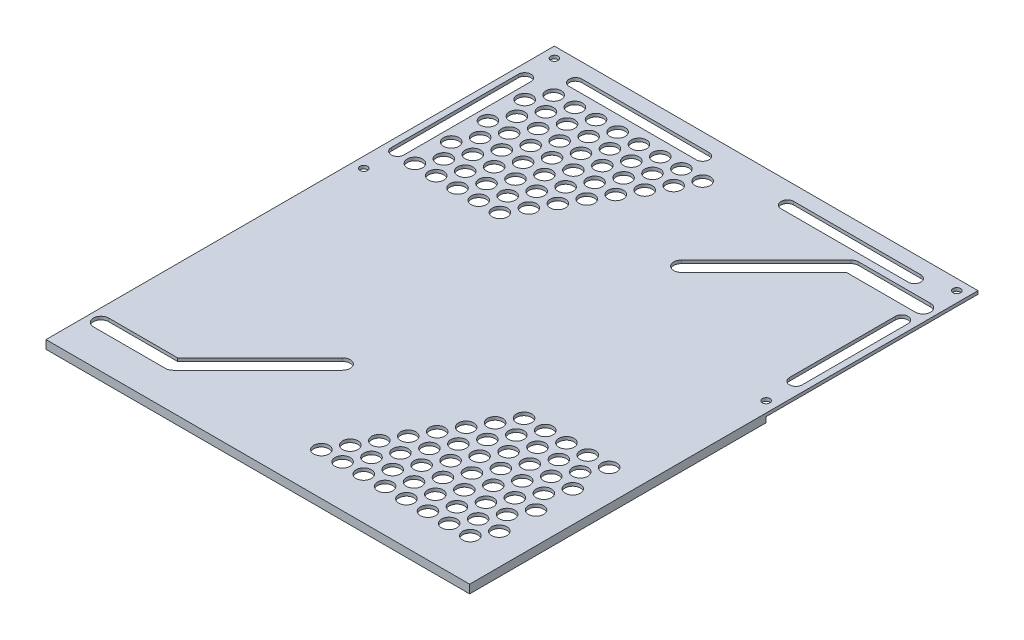
SolidWorks part; units mm, degrees
ref_plane "Front" through (0, 0, 0) normal (0, 0, 1) x (1, 0, 0)
ref_plane "Top" through (0, 0, 0) normal (0, 1, 0) x (1, 0, 0)
ref_plane "Right" through (0, 0, 0) normal (1, 0, 0) x (0, 0, -1)
sketch "Sketch1" plane through (0, 0, 0) normal (0, 1, 0) x (1, 0, 0)
  line L1 (0, 0) -> (127, 0)
  line L2 (0, 0) -> (0, 152.4)
  line L3 (0, 152.4) -> (127, 152.4)
  line L4 (127, 0) -> (127, 152.4)
  dimension "D1" = 152.4
  dimension "D2" = 127
extrude "Boss-Extrude1" add sketch "Sketch1" along normal blind 2.54
sketch "Sketch2" plane through (0, 2.54, 0) normal (0, 1, 0) x (1, 0, 0)
  line L0 (63.5, 152.4) -> (63.5, 0) construction
  line L1 (127, 152.4) -> (0, 152.4) construction
  line L2 (0, 0) -> (127, 0) construction
  line L3 (127, 76.2) -> (0, 76.2) construction
  line L4 (127, 0) -> (127, 152.4) construction
  line L5 (0, 152.4) -> (0, 0) construction
  circle A0 centre (63.5, 95.25) radius 1.016
  circle A1 centre (66.04, 95.25) radius 1.016
  circle A2 centre (68.58, 95.25) radius 1.016
  circle A3 centre (71.12, 95.25) radius 1.016
  circle A4 centre (73.66, 95.25) radius 1.016
  circle A5 centre (60.96, 95.25) radius 1.016
  circle A6 centre (58.42, 95.25) radius 1.016
  circle A7 centre (55.88, 95.25) radius 1.016
  circle A8 centre (53.34, 95.25) radius 1.016
  point P14 (63.5, 76.2)
  dimension "D1" = 2.032
  dimension "D4" = 57.15
  dimension "D2" = 5
  dimension "D3" = 5
sketch "Sketch5" plane through (0, 0, 0) normal (0, 1, 0) x (1, 0, 0)
  line L0 (63.5, 152.4) -> (63.5, 0) construction
  line L1 (0, 88.9) -> (127, 88.9)
  line L2 (0, 88.9) -> (0, 152.4)
  line L3 (0, 152.4) -> (127, 152.4)
  line L4 (127, 88.9) -> (127, 152.4)
  line L5 (0, 88.9) -> (127, 152.4) construction
  line L6 (0, 152.4) -> (127, 88.9) construction
  line L7 (127, 152.4) -> (0, 152.4) construction
  point P0 (63.5, 120.65)
  dimension "D1" = 63.5
  dimension "D2" = 127
extrude "Cut-Extrude2" cut sketch "Sketch5" along normal blind 1.5875
sketch "Sketch9" plane through (0, 2.54, 0) normal (0, 1, 0) x (1, 0, 0)
  line L0 (50.8, 38.1) -> (25.4, 12.7) construction
  line L1 (52.4164, 36.4836) -> (27.0164, 11.0836)
  line L2 (49.1836, 39.7164) -> (23.7836, 14.3164)
  line L3 (25.4, 12.7) -> (3.81, 12.7) construction
  line L4 (25.4, 10.414) -> (3.81, 10.414)
  line L5 (25.4, 14.986) -> (3.81, 14.986)
  line L6 (63.5, 152.4) -> (63.5, 0) construction
  line L7 (127, 76.2) -> (0, 76.2) construction
  line L8 (76.2, 114.3) -> (101.6, 139.7) construction
  line L9 (74.5836, 115.9164) -> (99.9836, 141.3164)
  line L10 (77.8164, 112.6836) -> (103.2164, 138.0836)
  line L11 (101.6, 139.7) -> (123.19, 139.7) construction
  line L12 (101.6, 141.986) -> (123.19, 141.986)
  line L13 (101.6, 137.414) -> (123.19, 137.414)
  arc A0 (52.4164, 36.4836) -> (49.1836, 39.7164) centre (50.8, 38.1) ccw
  arc A1 (23.7836, 14.3164) -> (27.0164, 11.0836) centre (25.4, 12.7) ccw
  arc A2 (25.4, 10.414) -> (25.4, 14.986) centre (25.4, 12.7) ccw
  arc A3 (3.81, 14.986) -> (3.81, 10.414) centre (3.81, 12.7) ccw
  arc A4 (74.5836, 115.9164) -> (77.8164, 112.6836) centre (76.2, 114.3) ccw
  arc A5 (103.2164, 138.0836) -> (99.9836, 141.3164) centre (101.6, 139.7) ccw
  arc A6 (101.6, 141.986) -> (101.6, 137.414) centre (101.6, 139.7) ccw
  arc A7 (123.19, 137.414) -> (123.19, 141.986) centre (123.19, 139.7) ccw
  point P2 (38.1, 25.4)
  point P7 (14.605, 12.7)
  point P23 (88.9, 127)
  point P28 (112.395, 139.7)
  point P35 (63.5, 76.2)
  dimension "D1" = 2.286
  dimension "D2" = 2.286
  dimension "D3" = 12.7
  dimension "D4" = 38.1
  dimension "D5" = 38.1
  dimension "D6" = 63.5
  dimension "D7" = 59.69
  dimension "D8" = 2
extrude "Cut-Extrude5" cut sketch "Sketch9" against normal through all contours A6 L9 A4 L10 L13 | A5 A6 L13 L10 | L13 A7 L12 A5 L10 | A2 L1 A0 L2 L5 | A1 A2 L5 L2 | L5 A3 L4 A1 L2 region at (39.3797, 2.54, -26.6777) region at (25.3939, 2.54, -12.7146) region at (12.7962, 2.54, -12.6976) region at (87.6203, 2.54, -125.7223) region at (101.6061, 2.54, -139.6854) region at (114.2038, 2.54, -139.7024)
sketch "Sketch10" plane through (0, 2.54, 0) normal (0, 1, 0) x (1, 0, 0)
  line L0 (127, 76.2) -> (0, 76.2) construction
  line L1 (63.5, 152.4) -> (63.5, 0) construction
  circle A1 centre (82.55, 12.7) radius 2.286
  circle A2 centre (85.7277, 18.2039) radius 2.286
  circle A3 centre (88.9053, 23.7078) radius 2.286
  circle A4 centre (92.083, 29.2117) radius 2.286
  circle A5 centre (95.2607, 34.7156) radius 2.286
  circle A6 centre (98.4384, 40.2195) radius 2.286
  circle A7 centre (101.616, 45.7234) radius 2.286
  circle A8 centre (104.7937, 51.2273) radius 2.286
  circle A9 centre (92.1245, 18.2039) radius 2.286
  circle A10 centre (95.3021, 23.7078) radius 2.286
  circle A11 centre (98.4798, 29.2117) radius 2.286
  circle A12 centre (101.6575, 34.7156) radius 2.286
  circle A13 centre (104.8352, 40.2195) radius 2.286
  circle A14 centre (108.0128, 45.7234) radius 2.286
  circle A15 centre (111.1905, 51.2273) radius 2.286
  circle A16 centre (88.9468, 12.7) radius 2.286
  circle A17 centre (98.5212, 18.2039) radius 2.286
  circle A18 centre (101.6989, 23.7078) radius 2.286
  circle A19 centre (104.8766, 29.2117) radius 2.286
  circle A20 centre (108.0543, 34.7156) radius 2.286
  circle A21 centre (111.2319, 40.2195) radius 2.286
  circle A22 centre (114.4096, 45.7234) radius 2.286
  circle A23 centre (117.5873, 51.2273) radius 2.286
  circle A24 centre (95.3436, 12.7) radius 2.286
  circle A25 centre (101.8105, 12.7) radius 2.286
  circle A26 centre (104.9882, 18.2039) radius 2.286
  circle A27 centre (108.1659, 23.7078) radius 2.286
  circle A28 centre (111.3436, 29.2117) radius 2.286
  circle A29 centre (114.5212, 34.7156) radius 2.286
  circle A30 centre (117.6989, 40.2195) radius 2.286
  circle A31 centre (108.1605, 12.7) radius 2.286
  circle A32 centre (111.3382, 18.2039) radius 2.286
  circle A33 centre (114.5159, 23.7078) radius 2.286
  circle A34 centre (117.6936, 29.2117) radius 2.286
  circle A35 centre (114.5105, 12.7) radius 2.286
  circle A36 centre (117.6882, 18.2039) radius 2.286
  circle A37 centre (44.582, 139.5661) radius 2.286
  circle A38 centre (41.4043, 134.0622) radius 2.286
  circle A39 centre (38.2266, 128.5583) radius 2.286
  circle A40 centre (35.0489, 123.0544) radius 2.286
  circle A41 centre (31.8713, 117.5505) radius 2.286
  circle A42 centre (28.6936, 112.0466) radius 2.286
  circle A43 centre (25.5159, 106.5427) radius 2.286
  circle A44 centre (22.3382, 101.0388) radius 2.286
  circle A45 centre (35.0075, 134.0622) radius 2.286
  circle A46 centre (31.8298, 128.5583) radius 2.286
  circle A47 centre (28.6522, 123.0544) radius 2.286
  circle A48 centre (25.4745, 117.5505) radius 2.286
  circle A49 centre (22.2968, 112.0466) radius 2.286
  circle A50 centre (19.1191, 106.5427) radius 2.286
  circle A51 centre (15.9415, 101.0388) radius 2.286
  circle A52 centre (38.1852, 139.5661) radius 2.286
  circle A53 centre (28.6107, 134.0622) radius 2.286
  circle A54 centre (25.433, 128.5583) radius 2.286
  circle A55 centre (22.2554, 123.0544) radius 2.286
  circle A56 centre (19.0777, 117.5505) radius 2.286
  circle A57 centre (15.9, 112.0466) radius 2.286
  circle A58 centre (12.7223, 106.5427) radius 2.286
  circle A59 centre (9.5447, 101.0388) radius 2.286
  circle A60 centre (31.7884, 139.5661) radius 2.286
  circle A61 centre (25.3214, 139.5661) radius 2.286
  circle A62 centre (22.1438, 134.0622) radius 2.286
  circle A63 centre (18.9661, 128.5583) radius 2.286
  circle A64 centre (15.7884, 123.0544) radius 2.286
  circle A65 centre (12.6107, 117.5505) radius 2.286
  circle A66 centre (9.4331, 112.0466) radius 2.286
  circle A67 centre (18.9714, 139.5661) radius 2.286
  circle A68 centre (15.7938, 134.0622) radius 2.286
  circle A69 centre (12.6161, 128.5583) radius 2.286
  circle A70 centre (9.4384, 123.0544) radius 2.286
  circle A71 centre (12.6214, 139.5661) radius 2.286
  circle A72 centre (9.4438, 134.0622) radius 2.286
  circle A73 centre (76.2, 12.7) radius 2.286
  circle A74 centre (79.3777, 18.2039) radius 2.286
  circle A75 centre (82.5553, 23.7078) radius 2.286
  circle A76 centre (85.733, 29.2117) radius 2.286
  circle A77 centre (88.9107, 34.7156) radius 2.286
  circle A78 centre (92.0884, 40.2195) radius 2.286
  circle A79 centre (95.266, 45.7234) radius 2.286
  circle A80 centre (98.4437, 51.2273) radius 2.286
  circle A81 centre (69.85, 12.7) radius 2.286
  circle A82 centre (73.0277, 18.2039) radius 2.286
  circle A83 centre (76.2053, 23.7078) radius 2.286
  circle A84 centre (79.383, 29.2117) radius 2.286
  circle A85 centre (82.5607, 34.7156) radius 2.286
  circle A86 centre (85.7384, 40.2195) radius 2.286
  circle A87 centre (88.916, 45.7234) radius 2.286
  circle A88 centre (92.0937, 51.2273) radius 2.286
  circle A89 centre (28.6882, 101.0388) radius 2.286
  circle A90 centre (31.8659, 106.5427) radius 2.286
  circle A91 centre (35.0436, 112.0466) radius 2.286
  circle A92 centre (38.2213, 117.5505) radius 2.286
  circle A93 centre (41.3989, 123.0544) radius 2.286
  circle A94 centre (44.5766, 128.5583) radius 2.286
  circle A95 centre (47.7543, 134.0622) radius 2.286
  circle A96 centre (50.932, 139.5661) radius 2.286
  circle A97 centre (35.0382, 101.0388) radius 2.286
  circle A98 centre (38.2159, 106.5427) radius 2.286
  circle A99 centre (41.3936, 112.0466) radius 2.286
  circle A100 centre (44.5713, 117.5505) radius 2.286
  circle A101 centre (47.7489, 123.0544) radius 2.286
  circle A102 centre (50.9266, 128.5583) radius 2.286
  circle A103 centre (54.1043, 134.0622) radius 2.286
  circle A104 centre (57.282, 139.5661) radius 2.286
  point P151 (63.566, 76.133)
  dimension "D1" = 3
  dimension "D3" = 2
  dimension "D4" = 4.572
  dimension "D5" = 63.5
  dimension "D6" = 19.05
  dimension "D2" = 2
  dimension "D7" = 8
  dimension "D8" = 2
  dimension "D10" = 3
  dimension "D11" = 3
  dimension "D9" = 2
extrude "Cut-Extrude6" cut sketch "Sketch10" against normal through all
sketch "Sketch12" plane through (0, 2.54, 0) normal (0, 1, 0) x (1, 0, 0)
  line L0 (76.2, 146.05) -> (114.3, 146.05) construction
  line L1 (76.2, 147.955) -> (114.3, 147.955)
  line L2 (76.2, 144.145) -> (114.3, 144.145)
  line L3 (63.5, 152.4) -> (63.5, 0) construction
  line L4 (63.5, 152.4) -> (63.5, 135.3884) construction
  line L5 (50.8, 146.05) -> (12.7, 146.05) construction
  line L6 (50.8, 147.955) -> (12.7, 147.955)
  line L7 (50.8, 144.145) -> (12.7, 144.145)
  line L8 (3.81, 139.7) -> (3.81, 101.6) construction
  line L9 (5.715, 139.7) -> (5.715, 101.6)
  line L10 (1.905, 139.7) -> (1.905, 101.6)
  line L11 (127, 152.4) -> (0, 152.4) construction
  arc A0 (76.2, 147.955) -> (76.2, 144.145) centre (76.2, 146.05) ccw
  arc A1 (114.3, 144.145) -> (114.3, 147.955) centre (114.3, 146.05) ccw
  arc A2 (50.8, 147.955) -> (50.8, 144.145) centre (50.8, 146.05) cw
  arc A3 (12.7, 144.145) -> (12.7, 147.955) centre (12.7, 146.05) cw
  arc A4 (5.715, 139.7) -> (1.905, 139.7) centre (3.81, 139.7) ccw
  arc A5 (1.905, 101.6) -> (5.715, 101.6) centre (3.81, 101.6) ccw
  point P2 (95.25, 146.05)
  point P14 (31.75, 146.05)
  point P21 (3.81, 120.65)
  dimension "D1" = 3.81
  dimension "D2" = 38.1
  dimension "D3" = 50.8
  dimension "D4" = 3.81
  dimension "D5" = 12.7
  dimension "D6" = 38.1
  dimension "D7" = 59.69
  dimension "D8" = 6.35
extrude "Cut-Extrude7" cut sketch "Sketch12" against normal through all and the other way through all
sketch "Sketch13" plane through (0, 0, 0) normal (0, -1, 0) x (1, 0, 0)
  line L0 (52.4164, -39.7164) -> (14.4021, -1.7021) construction
  line L1 (1.524, -12.7) -> (44.6383, -12.7) construction
  line L2 (49.1836, -39.7164) -> (52.4164, -36.4836) construction
  line L3 (3.81, -14.986) -> (3.81, -10.414) construction
  line L4 (50.8, -38.1) -> (25.4, -12.7) construction
  line L5 (47.4324, -41.4676) -> (22.0324, -16.0676)
  line L6 (54.1676, -34.7324) -> (28.7676, -9.3324)
  line L7 (25.4, -12.7) -> (3.81, -12.7) construction
  line L8 (25.4, -17.4625) -> (3.81, -17.4625)
  line L9 (25.4, -7.9375) -> (3.81, -7.9375)
  arc A0 (49.1836, -39.7164) -> (52.4164, -36.4836) centre (50.8, -38.1) ccw construction
  arc A1 (3.81, -10.414) -> (3.81, -14.986) centre (3.81, -12.7) ccw construction
  arc A2 (47.4324, -41.4676) -> (54.1676, -34.7324) centre (50.8, -38.1) ccw
  arc A3 (28.7676, -9.3324) -> (22.0324, -16.0676) centre (25.4, -12.7) ccw
  arc A4 (25.4, -17.4625) -> (25.4, -7.9375) centre (25.4, -12.7) ccw
  arc A5 (3.81, -7.9375) -> (3.81, -17.4625) centre (3.81, -12.7) ccw
  point P18 (25.4, -12.7)
  point P21 (38.1, -25.4)
  point P28 (14.605, -12.7)
  dimension "D1" = 9.525
  dimension "D2" = 9.525
extrude "Cut-Extrude8" cut sketch "Sketch13" against normal blind 1.5875 contours A4 L8 L5 A2 L6 | L8 A4 A3 L5 | L9 A5 L8 L5 A3 region at (40.7695, 0, -28.0604) region at (10.8344, 0, -12.6894) region at (25.3874, 0, -12.7304)
sketch "Sketch14" plane through (0, 0, 0) normal (0, -1, 0) x (1, 0, 0)
  line L0 (117.5873, -48.9413) -> (117.5873, -53.5133) construction
  line L1 (117.5873, -53.5133) -> (119.8733, -51.2273) construction
  line L2 (119.8733, -51.2273) -> (115.3013, -51.2273) construction
  line L3 (87.9693, -53.6085) -> (65.7256, -15.0812)
  line L4 (69.85, -7.9375) -> (114.5105, -7.9375)
  line L5 (92.0937, -55.9898) -> (117.5873, -55.9898)
  line L6 (118.683, -10.404) -> (121.5009, -15.35)
  line L7 (122.3498, -51.2418) -> (122.4507, -18.2184)
  circle A0 centre (69.85, -12.7) radius 4.7625
  circle A1 centre (92.0937, -51.2273) radius 4.7625
  circle A2 centre (114.5105, -12.7) radius 4.7625
  circle A3 centre (117.5873, -51.2273) radius 2.286 construction
  circle A4 centre (117.5873, -51.2273) radius 4.7625
  circle A5 centre (117.6882, -18.2039) radius 4.7625
  dimension "D1" = 9.525
  dimension "D2" = 9.525
  dimension "D3" = 9.525
  dimension "D4" = 9.525
  dimension "D5" = 9.525
extrude "Cut-Extrude9" cut sketch "Sketch14" against normal blind 1.5875 contours A5 A2 L4 A0 L3 A1 L5 A4 L7 | A0 | A5 A2 | A5 A2 | A4 | A1 | A2 A5 | A5 L6 A2 region at (97.5263, 0, -29.8912) region at (92.0937, 0, -51.2273) region at (69.85, 0, -12.7) region at (117.5873, 0, -51.2273) region at (114.0661, 0, -11.9303) region at (119.8852, 0, -13.2252) region at (116.0994, 0, -15.4519) region at (118.1326, 0, -18.9736)
sketch "Sketch15" plane through (0, 2.54, 0) normal (0, 1, 0) x (1, 0, 0)
  line L0 (127, 152.4) -> (0, 152.4) construction
  line L1 (0, 152.4) -> (0, 0) construction
  line L2 (63.5, 152.4) -> (63.5, 127.0009) construction
  circle A0 centre (3.175, 149.225) radius 1.1303
  circle A1 centre (3.175, 92.075) radius 1.1303
  circle A2 centre (123.825, 92.075) radius 1.1303
  circle A3 centre (123.825, 149.225) radius 1.1303
  dimension "D1" = 2.2606
  dimension "D2" = 3.175
  dimension "D3" = 3.175
  dimension "D4" = 2
extrude "Cut-Extrude10" cut sketch "Sketch15" against normal through all
sketch "Sketch16" plane through (0, 2.54, 0) normal (0, 1, 0) x (1, 0, 0)
  line L0 (123.19, 101.6) -> (123.19, 133.35) construction
  line L1 (121.285, 101.6) -> (121.285, 133.35)
  line L2 (125.095, 101.6) -> (125.095, 133.35)
  line L3 (63.5, 152.4) -> (63.5, 0) construction
  line L4 (127, 152.4) -> (0, 152.4) construction
  arc A0 (121.285, 101.6) -> (125.095, 101.6) centre (123.19, 101.6) ccw
  arc A1 (125.095, 133.35) -> (121.285, 133.35) centre (123.19, 133.35) ccw
  point P2 (123.19, 117.475)
  dimension "D1" = 1.905
  dimension "D2" = 59.69
  dimension "D3" = 31.75
  dimension "D4" = 19.05
extrude "Cut-Extrude11" cut sketch "Sketch16" against normal through all
